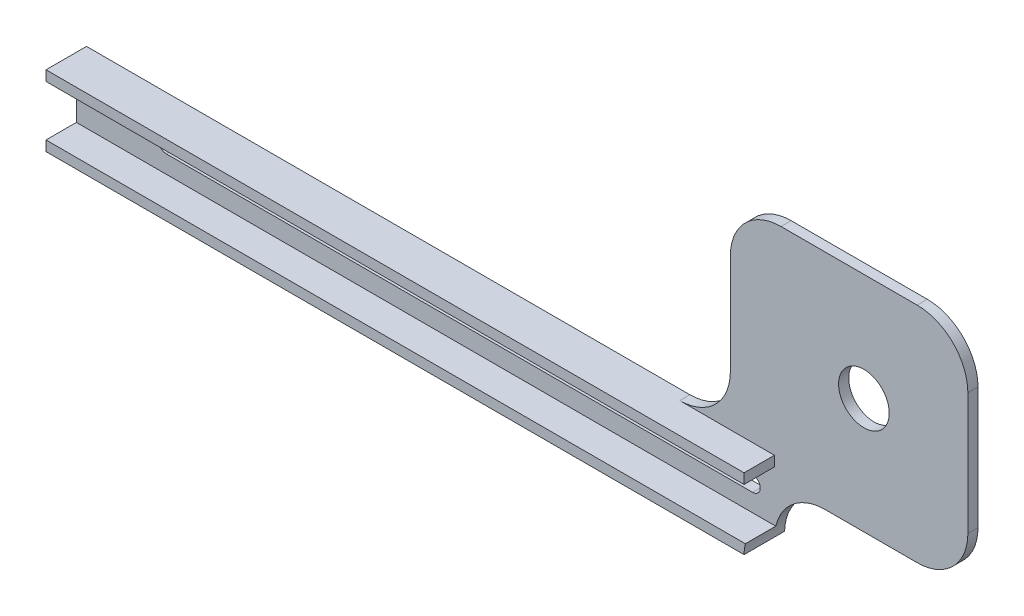
SolidWorks part; units mm, degrees
material "6061-T6 (SS)"
ref_plane "Front Plane" through (0, 0, 0) normal (0, 0, 1) x (1, 0, 0)
ref_plane "Top Plane" through (0, 0, 0) normal (0, 1, 0) x (1, 0, 0)
ref_plane "Right Plane" through (0, 0, 0) normal (1, 0, 0) x (0, 0, -1)
sketch "Sketch1" plane through (0, 0, -12.4578) normal (0, 0, 1) x (1, 0, 0)
  line L0 (-152.4792, 18.4041) -> (-5.4644, 18.4041) construction
  line L1 (-175.0671, 77.8027) -> (129.7329, 77.8027)
  line L2 (-175.0671, 77.8027) -> (-175.0671, -19.6959)
  line L3 (-175.0671, -19.6959) -> (0, -19.6959)
  line L4 (129.7329, 77.8027) -> (129.7329, 21.8576)
  line L5 (-152.4792, 20.3091) -> (-5.4644, 20.3091)
  line L6 (-152.4792, 16.4991) -> (-5.4644, 16.4991)
  line L7 (0, -19.6959) -> (0, 21.8576)
  line L8 (0, 21.8576) -> (129.7329, 21.8576)
  arc A0 (-152.4792, 20.3091) -> (-152.4792, 16.4991) centre (-152.4792, 18.4041) ccw
  arc A1 (-5.4644, 16.4991) -> (-5.4644, 20.3091) centre (-5.4644, 18.4041) ccw
  point P6 (-78.9718, 18.4041)
  dimension "D1" = 304.8
  dimension "D3" = 3.81
extrude "Boss-Extrude1" add sketch "Sketch1" against normal blind 2.54
sketch "Sketch2" plane through (0, 0, -12.4578) normal (0, 0, 1) x (1, 0, 0)
  circle A0 centre (22.4398, 50.8255) radius 6.35
  dimension "D1" = 12.7
extrude "Cut-Extrude1" cut sketch "Sketch2" against normal blind 2.54
sketch "Sketch3" plane through (0, 0, -12.4578) normal (0, 0, 1) x (1, 0, 0)
  line L0 (-175.0671, 77.8027) -> (-175.0671, -19.6959) construction
  line L1 (-175.0671, 24.7541) -> (0, 24.7541)
  line L2 (-175.0671, 24.7541) -> (-175.0671, 27.2941)
  line L3 (-175.0671, 27.2941) -> (0, 27.2941)
  line L4 (0, 24.7541) -> (0, 27.2941)
  line L5 (0, -19.6959) -> (0, 21.8576) construction
  line L6 (-175.0671, 12.0541) -> (0, 12.0541)
  line L7 (-175.0671, 12.0541) -> (-175.0671, 9.5141)
  line L8 (-175.0671, 9.5141) -> (0, 9.5141)
  line L9 (0, 12.0541) -> (0, 9.5141)
  line L10 (-152.4792, 16.4991) -> (-5.4644, 16.4991) construction
  line L11 (-5.4644, 20.3091) -> (-152.4792, 20.3091) construction
  dimension "D1" = 12.7
  dimension "D2" = 4.445
  dimension "D3" = 4.445
  dimension "D4" = 2.54
  dimension "D5" = 2.54
extrude "Boss-Extrude2" add sketch "Sketch3" along normal blind 7.62
sketch "Sketch4" plane through (0, 0, -12.4578) normal (0, 0, 1) x (1, 0, 0)
  line L0 (-175.0671, 9.5141) -> (0, 9.5141) construction
  line L1 (-175.0671, 9.5141) -> (0, 9.5141)
  line L2 (-175.0671, 9.5141) -> (-175.0671, -19.6959)
  line L3 (-175.0671, -19.6959) -> (0, -19.6959)
  line L4 (0, 9.5141) -> (0, -19.6959)
  line L5 (-175.0671, 9.5141) -> (-175.0671, -19.6959) construction
  line L6 (0, -19.6959) -> (0, 9.5141) construction
  line L7 (-175.0671, -19.6959) -> (0, -19.6959) construction
  line L9 (-175.0671, 27.2941) -> (-11.0501, 27.2941)
  line L10 (-175.0671, 27.2941) -> (-175.0671, 93.7693)
  line L11 (-175.0671, 93.7693) -> (-11.0501, 93.7693)
  line L12 (-11.0501, 27.2941) -> (-11.0501, 93.7693)
  line L13 (133.3353, 92.1463) -> (48.5129, 92.1463)
  line L14 (133.3353, 92.1463) -> (133.3353, 2.8595)
  line L15 (133.3353, 2.8595) -> (48.5129, 2.8595)
  line L16 (48.5129, 92.1463) -> (48.5129, 2.8595)
extrude "Cut-Extrude2" cut sketch "Sketch4" against normal blind 2.54
fillet "Fillet1" radius 12.7 5 edges at (-11.0501, 27.2941, -13.7278) (0, 21.8576, -13.7278) (48.5129, 21.8576, -13.7278) (48.5129, 77.8027, -13.7278) (-11.0501, 77.8027, -13.7278)
